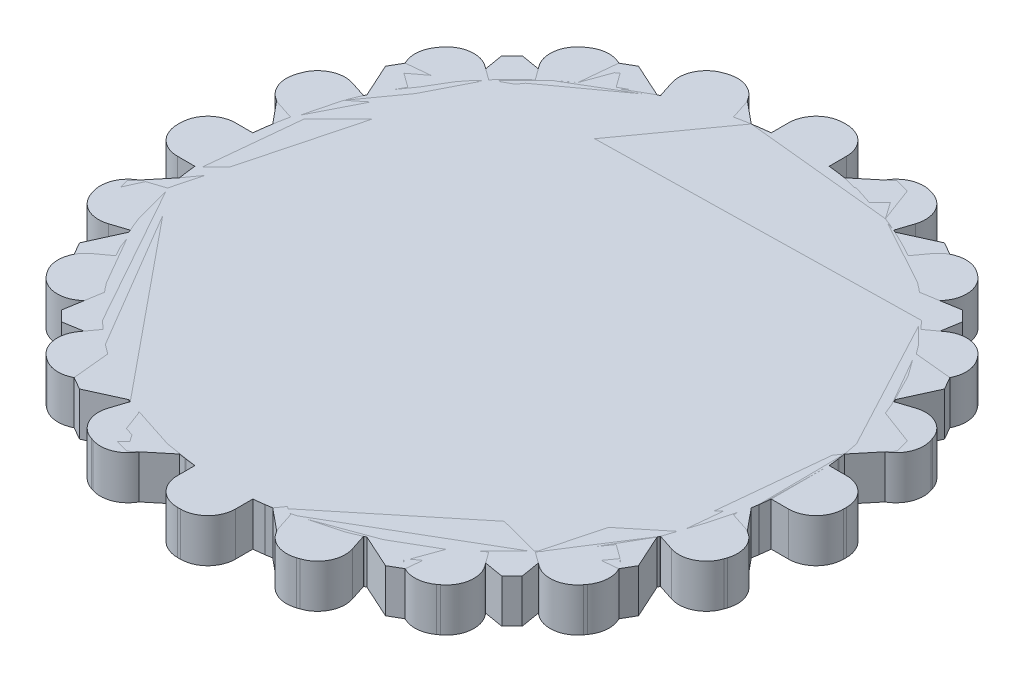
SolidWorks part; units mm, degrees
ref_plane "Front Plane" through (0, 0, 0) normal (0, 0, 1) x (1, 0, 0)
ref_plane "Top Plane" through (0, 0, 0) normal (0, 1, 0) x (1, 0, 0)
ref_plane "Right Plane" through (0, 0, 0) normal (1, 0, 0) x (0, 0, -1)
sketch "Sketch1" plane through (0, 0, 0) normal (0, 1, 0) x (1, 0, 0)
  line L111 (-0.5, 14.7462) -> (0.5, 14.7462)
  line L112 (0.5, 14.7462) -> (2, 12.5441)
  line L113 (-0.5, 14.7462) -> (-2, 12.5441)
  line L114 (6.433, 12.8885) -> (6.631, 10.2315)
  line L115 (5.567, 13.3885) -> (6.433, 12.8885)
  line L116 (5.567, 13.3885) -> (3.1669, 12.2315)
  line L117 (10.6423, 8.3132) -> (9.4853, 5.9131)
  line L118 (10.1423, 9.1792) -> (10.6423, 8.3132)
  line L119 (10.1423, 9.1792) -> (7.4853, 9.3772)
  line L120 (12, 2.2462) -> (9.798, 0.7462)
  line L121 (12, 3.2462) -> (12, 2.2462)
  line L122 (12, 3.2462) -> (9.798, 4.7462)
  line L123 (10.1423, -3.6868) -> (7.4853, -3.8849)
  line L124 (10.6423, -2.8208) -> (10.1423, -3.6868)
  line L125 (10.6423, -2.8208) -> (9.4853, -0.4208)
  line L126 (5.567, -7.8961) -> (3.1669, -6.7391)
  line L127 (6.433, -7.3961) -> (5.567, -7.8961)
  line L128 (6.433, -7.3961) -> (6.631, -4.7391)
  line L129 (-0.5, -9.2538) -> (-2, -7.0518)
  line L130 (0.5, -9.2538) -> (-0.5, -9.2538)
  line L131 (0.5, -9.2538) -> (2, -7.0518)
  line L132 (-6.433, -7.3961) -> (-6.631, -4.7391)
  line L133 (-5.567, -7.8961) -> (-6.433, -7.3961)
  line L134 (-5.567, -7.8961) -> (-3.1669, -6.7391)
  line L135 (-10.6423, -2.8208) -> (-9.4853, -0.4208)
  line L136 (-10.1423, -3.6868) -> (-10.6423, -2.8208)
  line L137 (-10.1423, -3.6868) -> (-7.4853, -3.8849)
  line L138 (-12, 3.2462) -> (-9.798, 4.7462)
  line L139 (-12, 2.2462) -> (-12, 3.2462)
  line L140 (-12, 2.2462) -> (-9.798, 0.7462)
  line L141 (-10.1423, 9.1792) -> (-7.4853, 9.3772)
  line L142 (-10.6423, 8.3132) -> (-10.1423, 9.1792)
  line L143 (-10.6423, 8.3132) -> (-9.4853, 5.9131)
  line L144 (-5.567, 13.3885) -> (-3.1669, 12.2315)
  line L145 (-6.433, 12.8885) -> (-5.567, 13.3885)
  line L146 (-6.433, 12.8885) -> (-6.631, 10.2315)
  arc A43 (-2, 12.5441) -> (-3.1669, 12.2315) centre (0, 2.7462) ccw
  arc A44 (-6.631, 10.2315) -> (-7.4853, 9.3772) centre (0, 2.7462) ccw
  arc A45 (-9.4853, 5.9131) -> (-9.798, 4.7462) centre (0, 2.7462) ccw
  arc A46 (-9.798, 0.7462) -> (-9.4853, -0.4208) centre (0, 2.7462) ccw
  arc A47 (-7.4853, -3.8849) -> (-6.631, -4.7391) centre (0, 2.7462) ccw
  arc A48 (-3.1669, -6.7391) -> (-2, -7.0518) centre (0, 2.7462) ccw
  arc A49 (2, -7.0518) -> (3.1669, -6.7391) centre (0, 2.7462) ccw
  arc A50 (6.631, -4.7391) -> (7.4853, -3.8849) centre (0, 2.7462) ccw
  arc A51 (9.4853, -0.4208) -> (9.798, 0.7462) centre (0, 2.7462) ccw
  arc A52 (9.798, 4.7462) -> (9.4853, 5.9131) centre (0, 2.7462) ccw
  arc A53 (7.4853, 9.3772) -> (6.631, 10.2315) centre (0, 2.7462) ccw
  arc A54 (3.1669, 12.2315) -> (2, 12.5441) centre (0, 2.7462) ccw
  point P1 (0, 0)
  point P6 (0, 0)
  point P8 (0, 0)
  point P9 (0, 0)
  point P12 (0, 2.7462)
  point P17 (0, 0)
  point P18 (0, 2.7462)
  point P22 (-2.5, 0.7462)
  point P63 (0, 0)
  point P68 (0, 0)
  point P69 (0, 2.7462)
  point P119 (0, 0)
  dimension "D1" = 20
  dimension "D8" = 12
sketch "Sketch2" plane through (0, 0, 0) normal (0, 1, 0) x (1, 0, 0)
  line L0 (-2, 0) -> (2, 0)
  line L1 (-23, -0.1) -> (-23, 0.1)
  line L2 (-21.1, 2) -> (-19.8997, 2)
  line L3 (-21.1, -2) -> (-19.8997, -2)
  line L4 (-20.6853, 4.6181) -> (-19.5438, 4.2472)
  line L5 (-19.4493, 8.4224) -> (-18.3078, 8.0515)
  line L6 (-21.9052, 7.0123) -> (-21.8434, 7.2025)
  line L7 (-18.2458, 10.7842) -> (-17.2748, 10.0787)
  line L8 (-15.8947, 14.0203) -> (-14.9237, 13.3148)
  line L9 (-18.6662, 13.4382) -> (-18.5486, 13.6)
  line L10 (-14.0203, 15.8947) -> (-13.3148, 14.9237)
  line L11 (-10.7842, 18.2458) -> (-10.0787, 17.2748)
  line L12 (-13.6, 18.5486) -> (-13.4382, 18.6662)
  line L13 (-8.4224, 19.4493) -> (-8.0515, 18.3078)
  line L14 (-4.6181, 20.6853) -> (-4.2472, 19.5438)
  line L15 (-7.2025, 21.8434) -> (-7.0123, 21.9052)
  line L16 (-2, 21.1) -> (-2, 19.8997)
  line L17 (2, 21.1) -> (2, 19.8997)
  line L18 (-0.1, 23) -> (0.1, 23)
  line L19 (4.6181, 20.6853) -> (4.2472, 19.5438)
  line L20 (8.4224, 19.4493) -> (8.0515, 18.3078)
  line L21 (7.0123, 21.9052) -> (7.2025, 21.8434)
  line L22 (10.7842, 18.2458) -> (10.0787, 17.2748)
  line L23 (14.0203, 15.8947) -> (13.3148, 14.9237)
  line L24 (13.4382, 18.6662) -> (13.6, 18.5486)
  line L25 (15.8947, 14.0203) -> (14.9237, 13.3148)
  line L26 (18.2458, 10.7842) -> (17.2748, 10.0787)
  line L27 (18.5486, 13.6) -> (18.6662, 13.4382)
  line L28 (19.4493, 8.4224) -> (18.3078, 8.0515)
  line L29 (20.6853, 4.6181) -> (19.5438, 4.2472)
  line L30 (21.8434, 7.2025) -> (21.9052, 7.0123)
  line L31 (21.1, 2) -> (19.8997, 2)
  line L32 (21.1, -2) -> (19.8997, -2)
  line L33 (23, 0.1) -> (23, -0.1)
  line L34 (20.6853, -4.6181) -> (19.5438, -4.2472)
  line L35 (19.4493, -8.4224) -> (18.3078, -8.0515)
  line L36 (21.9052, -7.0123) -> (21.8434, -7.2025)
  line L37 (18.2458, -10.7842) -> (17.2748, -10.0787)
  line L38 (15.8947, -14.0203) -> (14.9237, -13.3148)
  line L39 (18.6662, -13.4382) -> (18.5486, -13.6)
  line L40 (14.0203, -15.8947) -> (13.3148, -14.9237)
  line L41 (10.7842, -18.2458) -> (10.0787, -17.2748)
  line L42 (13.6, -18.5486) -> (13.4382, -18.6662)
  line L43 (8.4224, -19.4493) -> (8.0515, -18.3078)
  line L44 (4.6181, -20.6853) -> (4.2472, -19.5438)
  line L45 (7.2025, -21.8434) -> (7.0123, -21.9052)
  line L46 (2, -21.1) -> (2, -19.8997)
  line L47 (-2, -21.1) -> (-2, -19.8997)
  line L48 (0.1, -23) -> (-0.1, -23)
  line L49 (-4.6181, -20.6853) -> (-4.2472, -19.5438)
  line L50 (-8.4224, -19.4493) -> (-8.0515, -18.3078)
  line L51 (-7.0123, -21.9052) -> (-7.2025, -21.8434)
  line L52 (-10.7842, -18.2458) -> (-10.0787, -17.2748)
  line L53 (-14.0203, -15.8947) -> (-13.3148, -14.9237)
  line L54 (-13.4382, -18.6662) -> (-13.6, -18.5486)
  line L55 (-15.8947, -14.0203) -> (-14.9237, -13.3148)
  line L56 (-18.2458, -10.7842) -> (-17.2748, -10.0787)
  line L57 (-18.5486, -13.6) -> (-18.6662, -13.4382)
  line L58 (-19.4493, -8.4224) -> (-18.3078, -8.0515)
  line L59 (-20.6853, -4.6181) -> (-19.5438, -4.2472)
  line L60 (-21.8434, -7.2025) -> (-21.9052, -7.0123)
  arc A0 (-18.3078, -8.0515) -> (-17.2748, -10.0787) centre (0, 0) ccw
  arc A1 (-21.1, 2) -> (-23, 0.1) centre (-21.1, 0.1) ccw
  arc A2 (-21.1, -2) -> (-23, -0.1) centre (-21.1, -0.1) cw
  arc A3 (-20.6853, 4.6181) -> (-21.9052, 7.0123) centre (-20.0982, 6.4252) cw
  arc A4 (-19.4493, 8.4224) -> (-21.8434, 7.2025) centre (-20.0364, 6.6154) ccw
  arc A5 (-18.2458, 10.7842) -> (-18.6662, 13.4382) centre (-17.129, 12.3214) cw
  arc A6 (-15.8947, 14.0203) -> (-18.5486, 13.6) centre (-17.0115, 12.4832) ccw
  arc A7 (-14.0203, 15.8947) -> (-13.6, 18.5486) centre (-12.4832, 17.0115) cw
  arc A8 (-10.7842, 18.2458) -> (-13.4382, 18.6662) centre (-12.3214, 17.129) ccw
  arc A9 (-8.4224, 19.4493) -> (-7.2025, 21.8434) centre (-6.6154, 20.0364) cw
  arc A10 (-4.6181, 20.6853) -> (-7.0123, 21.9052) centre (-6.4252, 20.0982) ccw
  arc A11 (-2, 21.1) -> (-0.1, 23) centre (-0.1, 21.1) cw
  arc A12 (2, 21.1) -> (0.1, 23) centre (0.1, 21.1) ccw
  arc A13 (4.6181, 20.6853) -> (7.0123, 21.9052) centre (6.4252, 20.0982) cw
  arc A14 (8.4224, 19.4493) -> (7.2025, 21.8434) centre (6.6154, 20.0364) ccw
  arc A15 (10.7842, 18.2458) -> (13.4382, 18.6662) centre (12.3214, 17.129) cw
  arc A16 (14.0203, 15.8947) -> (13.6, 18.5486) centre (12.4832, 17.0115) ccw
  arc A17 (15.8947, 14.0203) -> (18.5486, 13.6) centre (17.0115, 12.4832) cw
  arc A18 (18.2458, 10.7842) -> (18.6662, 13.4382) centre (17.129, 12.3214) ccw
  arc A19 (19.4493, 8.4224) -> (21.8434, 7.2025) centre (20.0364, 6.6154) cw
  arc A20 (20.6853, 4.6181) -> (21.9052, 7.0123) centre (20.0982, 6.4252) ccw
  arc A21 (21.1, 2) -> (23, 0.1) centre (21.1, 0.1) cw
  arc A22 (21.1, -2) -> (23, -0.1) centre (21.1, -0.1) ccw
  arc A23 (20.6853, -4.6181) -> (21.9052, -7.0123) centre (20.0982, -6.4252) cw
  arc A24 (19.4493, -8.4224) -> (21.8434, -7.2025) centre (20.0364, -6.6154) ccw
  arc A25 (18.2458, -10.7842) -> (18.6662, -13.4382) centre (17.129, -12.3214) cw
  arc A26 (15.8947, -14.0203) -> (18.5486, -13.6) centre (17.0115, -12.4832) ccw
  arc A27 (14.0203, -15.8947) -> (13.6, -18.5486) centre (12.4832, -17.0115) cw
  arc A28 (10.7842, -18.2458) -> (13.4382, -18.6662) centre (12.3214, -17.129) ccw
  arc A29 (8.4224, -19.4493) -> (7.2025, -21.8434) centre (6.6154, -20.0364) cw
  arc A30 (4.6181, -20.6853) -> (7.0123, -21.9052) centre (6.4252, -20.0982) ccw
  arc A31 (2, -21.1) -> (0.1, -23) centre (0.1, -21.1) cw
  arc A32 (-2, -21.1) -> (-0.1, -23) centre (-0.1, -21.1) ccw
  arc A33 (-4.6181, -20.6853) -> (-7.0123, -21.9052) centre (-6.4252, -20.0982) cw
  arc A34 (-8.4224, -19.4493) -> (-7.2025, -21.8434) centre (-6.6154, -20.0364) ccw
  arc A35 (-10.7842, -18.2458) -> (-13.4382, -18.6662) centre (-12.3214, -17.129) cw
  arc A36 (-14.0203, -15.8947) -> (-13.6, -18.5486) centre (-12.4832, -17.0115) ccw
  arc A37 (-15.8947, -14.0203) -> (-18.5486, -13.6) centre (-17.0115, -12.4832) cw
  arc A38 (-18.2458, -10.7842) -> (-18.6662, -13.4382) centre (-17.129, -12.3214) ccw
  arc A39 (-19.4493, -8.4224) -> (-21.8434, -7.2025) centre (-20.0364, -6.6154) cw
  arc A40 (-20.6853, -4.6181) -> (-21.9052, -7.0123) centre (-20.0982, -6.4252) ccw
  arc A41 (-19.8997, -2) -> (-19.5438, -4.2472) centre (0, 0) ccw
  arc A42 (-19.5438, 4.2472) -> (-19.8997, 2) centre (0, 0) ccw
  arc A43 (-17.2748, 10.0787) -> (-18.3078, 8.0515) centre (0, 0) ccw
  arc A44 (-13.3148, 14.9237) -> (-14.9237, 13.3148) centre (0, 0) ccw
  arc A45 (-8.0515, 18.3078) -> (-10.0787, 17.2748) centre (0, 0) ccw
  arc A46 (-2, 19.8997) -> (-4.2472, 19.5438) centre (0, 0) ccw
  arc A47 (4.2472, 19.5438) -> (2, 19.8997) centre (0, 0) ccw
  arc A48 (10.0787, 17.2748) -> (8.0515, 18.3078) centre (0, 0) ccw
  arc A49 (14.9237, 13.3148) -> (13.3148, 14.9237) centre (0, 0) ccw
  arc A50 (18.3078, 8.0515) -> (17.2748, 10.0787) centre (0, 0) ccw
  arc A51 (19.8997, 2) -> (19.5438, 4.2472) centre (0, 0) ccw
  arc A52 (19.5438, -4.2472) -> (19.8997, -2) centre (0, 0) ccw
  arc A53 (17.2748, -10.0787) -> (18.3078, -8.0515) centre (0, 0) ccw
  arc A54 (13.3148, -14.9237) -> (14.9237, -13.3148) centre (0, 0) ccw
  arc A55 (8.0515, -18.3078) -> (10.0787, -17.2748) centre (0, 0) ccw
  arc A56 (2, -19.8997) -> (4.2472, -19.5438) centre (0, 0) ccw
  arc A57 (-10.0787, -17.2748) -> (-8.0515, -18.3078) centre (0, 0) ccw
  arc A58 (-4.2472, -19.5438) -> (-2, -19.8997) centre (0, 0) ccw
  arc A59 (-14.9237, -13.3148) -> (-13.3148, -14.9237) centre (0, 0) ccw
  point P6 (0, 0)
  point P10 (-23, 2)
  point P170 (0, 0)
  dimension "D1" = 40
  dimension "D4" = 1.9
  dimension "D5" = 20
extrude "Boss-Extrude3" add sketch "Sketch2" along normal blind 3 contours L55 A59 L53 A36 L54 A35 L52 A57 L50 A34 L51 A33 L49 A58 L47 A32 L48 A31 L46 A56 L44 A30 L45 A29 L43 A55 L41 A28 L42 A27 L40 A54 L38 A26 L39 A25 L37 A53 L35 A24 L36 A23 L34 A52 L32 A22 L33 A21 region at (-22.3495, 0, 0)
sketch "Sketch3" plane through (0, 0, 0) normal (0, 1, 0) x (1, 0, 0)
  line L0 (-22, 0) -> (22, 0)
  line L1 (22, -0.5) -> (22, 0.5)
  line L2 (22, 0.5) -> (19.8997, 2)
  line L3 (22, -0.5) -> (19.8997, -2)
  line L4 (21.3798, -5.2111) -> (19.7393, -3.2186)
  line L5 (21.121, -6.177) -> (21.3798, -5.2111)
  line L6 (21.121, -6.177) -> (18.704, -7.0823)
  line L7 (19.3026, -10.567) -> (18.2337, -8.2178)
  line L8 (18.8026, -11.433) -> (19.3026, -10.567)
  line L9 (18.8026, -11.433) -> (16.2337, -11.6819)
  line L10 (15.9099, -15.2028) -> (15.4855, -12.657)
  line L11 (15.2028, -15.9099) -> (15.9099, -15.2028)
  line L12 (15.2028, -15.9099) -> (12.657, -15.4855)
  line L13 (11.433, -18.8026) -> (11.6819, -16.2337)
  line L14 (10.567, -19.3026) -> (11.433, -18.8026)
  line L15 (10.567, -19.3026) -> (8.2178, -18.2337)
  line L16 (6.177, -21.121) -> (7.0823, -18.704)
  line L17 (5.2111, -21.3798) -> (6.177, -21.121)
  line L18 (5.2111, -21.3798) -> (3.2186, -19.7393)
  line L19 (0.5, -22) -> (2, -19.8997)
  line L20 (-0.5, -22) -> (0.5, -22)
  line L21 (-0.5, -22) -> (-2, -19.8997)
  line L22 (-5.2111, -21.3798) -> (-3.2186, -19.7393)
  line L23 (-6.177, -21.121) -> (-5.2111, -21.3798)
  line L24 (-6.177, -21.121) -> (-7.0823, -18.704)
  line L25 (-10.567, -19.3026) -> (-8.2178, -18.2337)
  line L26 (-11.433, -18.8026) -> (-10.567, -19.3026)
  line L27 (-11.433, -18.8026) -> (-11.6819, -16.2337)
  line L28 (-15.2028, -15.9099) -> (-12.657, -15.4855)
  line L29 (-15.9099, -15.2028) -> (-15.2028, -15.9099)
  line L30 (-15.9099, -15.2028) -> (-15.4855, -12.657)
  line L31 (-18.8026, -11.433) -> (-16.2337, -11.6819)
  line L32 (-19.3026, -10.567) -> (-18.8026, -11.433)
  line L33 (-19.3026, -10.567) -> (-18.2337, -8.2178)
  line L34 (-21.121, -6.177) -> (-18.704, -7.0823)
  line L35 (-21.3798, -5.2111) -> (-21.121, -6.177)
  line L36 (-21.3798, -5.2111) -> (-19.7393, -3.2186)
  line L37 (-22, -0.5) -> (-19.8997, -2)
  line L38 (-22, 0.5) -> (-22, -0.5)
  line L39 (-22, 0.5) -> (-19.8997, 2)
  line L40 (-21.3798, 5.2111) -> (-19.7393, 3.2186)
  line L41 (-21.121, 6.177) -> (-21.3798, 5.2111)
  line L42 (-21.121, 6.177) -> (-18.704, 7.0823)
  line L43 (-19.3026, 10.567) -> (-18.2337, 8.2178)
  line L44 (-18.8026, 11.433) -> (-19.3026, 10.567)
  line L45 (-18.8026, 11.433) -> (-16.2337, 11.6819)
  line L46 (-15.9099, 15.2028) -> (-15.4855, 12.657)
  line L47 (-15.2028, 15.9099) -> (-15.9099, 15.2028)
  line L48 (-15.2028, 15.9099) -> (-12.657, 15.4855)
  line L49 (-11.433, 18.8026) -> (-11.6819, 16.2337)
  line L50 (-10.567, 19.3026) -> (-11.433, 18.8026)
  line L51 (-10.567, 19.3026) -> (-8.2178, 18.2337)
  line L52 (-6.177, 21.121) -> (-7.0823, 18.704)
  line L53 (-5.2111, 21.3798) -> (-6.177, 21.121)
  line L54 (-5.2111, 21.3798) -> (-3.2186, 19.7393)
  line L55 (-0.5, 22) -> (-2, 19.8997)
  line L56 (0.5, 22) -> (-0.5, 22)
  line L57 (0.5, 22) -> (2, 19.8997)
  line L58 (5.2111, 21.3798) -> (3.2186, 19.7393)
  line L59 (6.177, 21.121) -> (5.2111, 21.3798)
  line L60 (6.177, 21.121) -> (7.0823, 18.704)
  line L61 (10.567, 19.3026) -> (8.2178, 18.2337)
  line L62 (11.433, 18.8026) -> (10.567, 19.3026)
  line L63 (11.433, 18.8026) -> (11.6819, 16.2337)
  line L64 (15.2028, 15.9099) -> (12.657, 15.4855)
  line L65 (15.9099, 15.2028) -> (15.2028, 15.9099)
  line L66 (15.9099, 15.2028) -> (15.4855, 12.657)
  line L67 (18.8026, 11.433) -> (16.2337, 11.6819)
  line L68 (19.3026, 10.567) -> (18.8026, 11.433)
  line L69 (19.3026, 10.567) -> (18.2337, 8.2178)
  line L70 (21.121, 6.177) -> (18.704, 7.0823)
  line L71 (21.3798, 5.2111) -> (21.121, 6.177)
  line L72 (21.3798, 5.2111) -> (19.7393, 3.2186)
  arc A0 (-8.2178, -18.2337) -> (-7.0823, -18.704) centre (0, 0) ccw
  arc A1 (-12.657, -15.4855) -> (-11.6819, -16.2337) centre (0, 0) ccw
  arc A2 (-16.2337, -11.6819) -> (-15.4855, -12.657) centre (0, 0) ccw
  arc A3 (-18.704, -7.0823) -> (-18.2337, -8.2178) centre (0, 0) ccw
  arc A4 (-19.8997, -2) -> (-19.7393, -3.2186) centre (0, 0) ccw
  arc A5 (-19.7393, 3.2186) -> (-19.8997, 2) centre (0, 0) ccw
  arc A6 (-18.2337, 8.2178) -> (-18.704, 7.0823) centre (0, 0) ccw
  arc A7 (-15.4855, 12.657) -> (-16.2337, 11.6819) centre (0, 0) ccw
  arc A8 (-11.6819, 16.2337) -> (-12.657, 15.4855) centre (0, 0) ccw
  arc A9 (-7.0823, 18.704) -> (-8.2178, 18.2337) centre (0, 0) ccw
  arc A10 (-2, 19.8997) -> (-3.2186, 19.7393) centre (0, 0) ccw
  arc A11 (3.2186, 19.7393) -> (2, 19.8997) centre (0, 0) ccw
  arc A12 (8.2178, 18.2337) -> (7.0823, 18.704) centre (0, 0) ccw
  arc A13 (12.657, 15.4855) -> (11.6819, 16.2337) centre (0, 0) ccw
  arc A14 (16.2337, 11.6819) -> (15.4855, 12.657) centre (0, 0) ccw
  arc A15 (18.704, 7.0823) -> (18.2337, 8.2178) centre (0, 0) ccw
  arc A16 (19.8997, 2) -> (19.7393, 3.2186) centre (0, 0) ccw
  arc A17 (19.7393, -3.2186) -> (19.8997, -2) centre (0, 0) ccw
  arc A18 (18.2337, -8.2178) -> (18.704, -7.0823) centre (0, 0) ccw
  arc A19 (-3.2186, -19.7393) -> (-2, -19.8997) centre (0, 0) ccw
  arc A20 (2, -19.8997) -> (3.2186, -19.7393) centre (0, 0) ccw
  arc A21 (7.0823, -18.704) -> (8.2178, -18.2337) centre (0, 0) ccw
  arc A22 (11.6819, -16.2337) -> (12.657, -15.4855) centre (0, 0) ccw
  arc A23 (15.4855, -12.657) -> (16.2337, -11.6819) centre (0, 0) ccw
  point P6 (0, 0)
  point P7 (0, -12.952)
  point P8 (-6.2727, 0)
  point P9 (11.4668, 0)
  point P10 (0, 0)
  point P108 (0, 0)
  dimension "D1" = 40
  dimension "D2" = 22
  dimension "D3" = 2
  dimension "D4" = 24
extrude "Boss-Extrude5" add sketch "Sketch3" along normal blind 3 separate body contours L2 A16 L72 L71 L70 A15 L69 L68 L67 A14 L66 L65 L64 A13 L63 L62 L61 A12 L60 L59 L58 A11 L57 L56 L55 A10 L54 L53 L52 A9 L51 L50 L49 A8 L48 L47 L46 A7 L45 L44 L43 A6 L42 L41 L40 A5 L39 L38 L0 L1 | L10 A23 L9 L8 L7 A18 L6 L5 L4 A17 L3 L1 L0 L38 L37 A4 L36 L35 L34 A3 L33 L32 L31 A2 L30 L29 L28 A1 L27 L26 L25 A0 L24 L23 L22 A19 L21 L20 L19 A20 L18 L17 L16 A21 L15 L14 L13 A22 L12 L11 region at (0, 0, -8.8989) region at (0, 0, 8.8989)
extrude "Boss-Extrude6" add sketch "Sketch1" along normal blind 3 separate body
